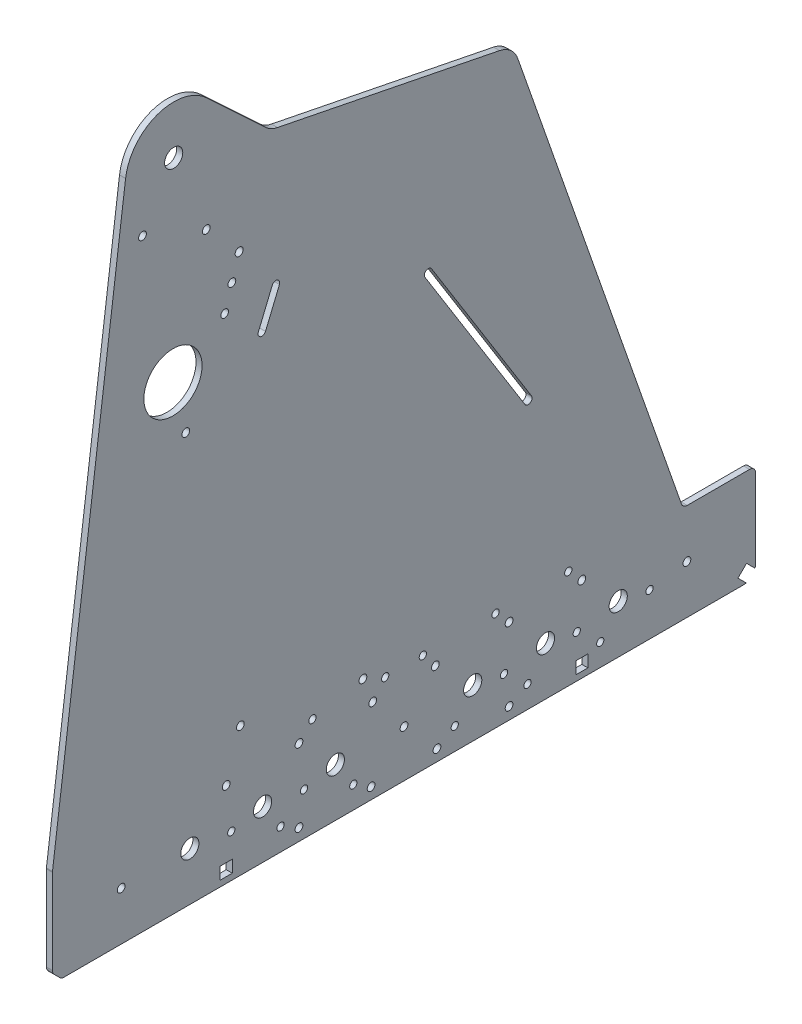
SolidWorks part; units mm, degrees
ref_plane "Front Plane" through (0, 0, 0) normal (0, 0, 1) x (1, 0, 0)
ref_plane "Top Plane" through (0, 0, 0) normal (0, 1, 0) x (1, 0, 0)
ref_plane "Right Plane" through (0, 0, 0) normal (1, 0, 0) x (0, 0, -1)
sketch "Sketch1" plane through (0, 0, 0) normal (1, 0, 0) x (0, 0, -1)
  line L0 (-184.15, -24.6062) -> (184.15, -24.6062)
  line L1 (184.15, -24.6062) -> (184.15, 26.1938)
  line L2 (184.15, 26.1938) -> (146.05, 26.1937)
  line L3 (146.05, 26.1937) -> (57.15, 280.1938)
  line L5 (-145.839, 321.5609) -> (-184.15, 26.1938)
  line L6 (-184.15, 26.1938) -> (-184.15, -24.6062)
  line L7 (-184.15, 350.0437) -> (184.15, 350.0437) construction
  line L8 (57.15, 280.1938) -> (-69.85, 305.5938)
  line L9 (-69.85, 305.5938) -> (-103.3099, 336.854)
  arc A0 (-103.3099, 336.854) -> (-145.839, 321.5609) centre (-120.65, 318.2937) ccw
  point P8 (0, -24.6062)
  dimension "D1" = 368.3
  dimension "D7" = 25.4
  dimension "D2" = 50.8
  dimension "D3" = 38.1
  dimension "D4" = 24.6062
  dimension "D5" = 374.65
  dimension "D6" = 304.8
  dimension "D8" = 342.9
  dimension "D9" = 127
  dimension "D10" = 304.8
  dimension "D11" = 25.4
  dimension "D12" = 127
extrude "Boss-Extrude1" add sketch "Sketch1" along normal blind 3.175
chamfer "Chamfer1" distance 4.7625 angle 45 2 edges at (1.5875, -24.6062, 184.15) (1.5875, -24.6062, -184.15)
fillet "Fillet1" radius 12.7 2 edges at (1.5875, 305.5938, 69.85) (1.5875, 280.1938, -57.15)
fillet "Fillet2" radius 3.175 3 edges at (1.5875, 26.1938, 184.15) (1.5875, 26.1938, -184.15) (1.5875, 26.1937, -146.05)
fillet "Fillet3" radius 3.175 4 edges at (1.5875, -19.8438, -184.15) (1.5875, -24.6062, -179.3875) (1.5875, -19.8437, 184.15) (1.5875, -24.6062, 179.3875)
sketch "Sketch16" plane through (3.175, 0, 0) normal (1, 0, 0) x (0, 0, -1)
  circle A0 centre (112.1746, 0.7937) radius 4.7625
  circle A1 centre (74.0746, 0.7937) radius 4.7625
  circle A2 centre (35.9746, 0.7937) radius 4.7625
  circle A3 centre (-35.9746, 0.7938) radius 4.7625
  circle A4 centre (-74.0746, 0.7938) radius 4.7625
  circle A5 centre (-112.1746, 0.7937) radius 4.7625
  dimension "D1" = 9.525
  dimension "D2" = 9.525
extrude "Cut-Extrude1" cut sketch "Sketch16" against normal up to next
sketch "Sketch25" plane through (3.175, 0, 0) normal (1, 0, 0) x (0, 0, -1)
  circle A0 centre (102.7672, -13.0003) radius 1.905 construction
  circle A1 centre (86.0486, 27.3622) radius 1.905 construction
  circle A2 centre (128.5804, -2.3081) radius 1.905 construction
  circle A3 centre (102.7672, -13.0003) radius 1.905
  circle A4 centre (86.0486, 27.3622) radius 1.905
  circle A5 centre (128.5804, -2.3081) radius 1.905
  circle A6 centre (64.6672, -13.0003) radius 1.905 construction
  circle A8 centre (-9.8486, 27.3622) radius 1.905 construction
  circle A10 centre (-47.9486, 27.3622) radius 1.905 construction
  circle A11 centre (-90.4804, -2.3081) radius 1.905 construction
  circle A12 centre (-64.6672, -13.0003) radius 1.905 construction
  circle A14 centre (-52.3804, -2.3081) radius 1.905 construction
  circle A15 centre (-26.5672, -13.0003) radius 1.905 construction
  circle A16 centre (9.8486, 27.3622) radius 1.905 construction
  circle A17 centre (26.5672, -13.0003) radius 1.905 construction
  circle A18 centre (47.9486, 27.3622) radius 1.905 construction
  circle A19 centre (52.3804, -2.3081) radius 1.905 construction
  circle A20 centre (90.4804, -2.3081) radius 1.905 construction
  circle A21 centre (-9.8486, 27.3622) radius 1.905
  circle A23 centre (-47.9486, 27.3622) radius 1.905
  circle A24 centre (-90.4804, -2.3081) radius 1.905
  circle A25 centre (-64.6672, -13.0003) radius 1.905
  circle A27 centre (-52.3804, -2.3081) radius 1.905
  circle A28 centre (-26.5672, -13.0003) radius 1.905
  circle A29 centre (9.8486, 27.3622) radius 1.905
  circle A30 centre (26.5672, -13.0003) radius 1.905
  circle A31 centre (47.9486, 27.3622) radius 1.905
  circle A32 centre (64.6672, -13.0003) radius 1.905
  circle A33 centre (52.3804, -2.3081) radius 1.905
  circle A34 centre (90.4804, -2.3081) radius 1.905
extrude "Cut-Extrude4" cut sketch "Sketch25" against normal up to next
sketch "Sketch23" plane through (3.175, 0, 0) normal (1, 0, 0) x (0, 0, -1)
  point P0 (-55.0246, -18.3223)
  point P3 (-55.0246, 19.9098)
  point P6 (-93.1246, 19.9098)
  point P9 (-17.2515, -18.6426)
  point P12 (-16.4124, 19.3854)
  point P15 (16.4124, 19.3854)
  point P18 (17.2515, -18.6426)
  point P21 (55.0246, -18.3223)
  point P27 (93.1246, 19.9098)
  point P30 (55.0246, 19.9098)
hole_wizard "#8 (0.16) Diameter Hole1" positions "Sketch23" profile "Sketch24" hole size "#8" standard "ANSI Inch" end condition up to next
sketch "Sketch24" plane through (3.175, -18.3223, 55.0246) normal (0, 1, 0) x (0, 0, -1)
  line L0 (0, 0) -> (0, 3.175)
  line L1 (0, 3.175) -> (2.032, 3.175)
  line L2 (2.032, 3.175) -> (2.032, 0)
  line L5 (2.032, 0) -> (0, 0)
  line L11 (0, -6.35) -> (0, 107.95) construction
  dimension "Thru Hole Dia." = 4.064
  dimension "Thru Hole Depth" = 3.175
sketch "Sketch22" plane through (3.175, 0, 0) normal (1, 0, 0) x (0, 0, -1)
  line L0 (-96.2996, -15.1473) -> (-89.9496, -15.1473) construction
  line L1 (-96.2996, -15.1473) -> (-89.9496, -15.1473)
  line L2 (-96.2996, -15.1473) -> (-96.2996, -21.4973)
  line L3 (-96.2996, -21.4973) -> (-89.9496, -21.4973)
  line L4 (-89.9496, -15.1473) -> (-89.9496, -21.4973)
  line L5 (-96.2996, -15.1473) -> (-89.9496, -21.4973) construction
  line L6 (-96.2996, -21.4973) -> (-89.9496, -15.1473) construction
  line L7 (-89.9496, -15.1473) -> (-89.9496, -19.8734) construction
  line L77 (179.3875, -24.6062) -> (183.8776, -20.1161)
  line L78 (179.3875, -24.6062) -> (174.8974, -20.1161)
  line L79 (183.8776, -20.1161) -> (179.3875, -15.626)
  line L80 (174.8974, -20.1161) -> (179.3875, -15.626)
  line L81 (180.3174, -23.6763) -> (183.2201, -20.7737) construction
  line L82 (-178.0724, -24.6062) -> (178.0724, -24.6062) construction
  line L84 (89.9496, -21.4973) -> (96.2996, -21.4973)
  line L85 (89.9496, -21.4973) -> (89.9496, -15.1473)
  line L86 (89.9496, -15.1473) -> (96.2996, -15.1473)
  line L87 (96.2996, -21.4973) -> (96.2996, -15.1473)
  line L88 (89.9496, -21.4973) -> (96.2996, -15.1473) construction
  line L89 (89.9496, -15.1473) -> (96.2996, -21.4973) construction
  point P0 (-93.1246, -18.3223)
  point P19 (93.1246, -18.3223)
  dimension "D1" = 6.35
  dimension "D2" = 6.35
extrude "Cut-Extrude3" cut sketch "Sketch22" against normal up to next
sketch "Sketch21" plane through (3.175, 0, 0) normal (1, 0, 0) x (0, 0, -1)
  circle A0 centre (-148.1579, 0.7937) radius 2.032
  circle A2 centre (0, 0) radius 2.032
  circle A3 centre (148.1579, 0.7938) radius 2.032
  dimension "D1" = 4.064
extrude "Cut-Extrude2" cut sketch "Sketch21" against normal up to next
sketch "Sketch26" plane through (3.175, 0, 0) normal (1, 0, 0) x (0, 0, -1)
  line L0 (-145.839, 321.5609) -> (-184.1236, 26.3971) construction
  line L1 (-178.0724, -24.6062) -> (178.0724, -24.6062) construction
  circle A0 centre (-121.0218, 216.6937) radius 15.24
  dimension "D1" = 30.48
  dimension "D2" = 38.1
  dimension "D3" = 241.3
extrude "Cut-Extrude5" cut sketch "Sketch26" against normal through all
sketch "Sketch27" plane through (3.175, 0, 0) normal (1, 0, 0) x (0, 0, -1)
  circle A0 centre (-120.65, 318.2937) radius 4.7625
  dimension "D1" = 9.525
extrude "Cut-Extrude6" cut sketch "Sketch27" against normal through all
sketch "Sketch28" plane through (3.175, 0, 0) normal (1, 0, 0) x (0, 0, -1)
  line L0 (-120.65, 318.2937) -> (-103.5612, 277.2599) construction
  line L1 (-103.5612, 277.2599) -> (-86.3654, 258.566) construction
  line L2 (-86.3654, 258.566) -> (-90.1612, 246.4465) construction
  line L3 (-90.1612, 246.4465) -> (-93.9569, 234.327) construction
  line L4 (-145.839, 321.5609) -> (-184.1236, 26.3971) construction
  circle A0 centre (-93.9569, 234.327) radius 2.032
  circle A1 centre (-90.1612, 246.4465) radius 2.032
  circle A2 centre (-86.3654, 258.566) radius 2.0955
  circle A3 centre (-103.5612, 277.2599) radius 2.032
  dimension "D4" = 4.064
  dimension "D5" = 4.191
  dimension "D6" = 4.064
  dimension "D1" = 25.4
  dimension "D2" = 44.45
  dimension "D3" = 12.7
  dimension "D7" = 30
  dimension "D8" = 120
  dimension "D9" = 160
extrude "Cut-Extrude7" cut sketch "Sketch28" against normal through all
sketch "Sketch29" plane through (3.175, 0, 0) normal (1, 0, 0) x (0, 0, -1)
  line L0 (-145.839, 321.5609) -> (-184.1236, 26.3971) construction
  line L1 (-67.1375, 233.9197) -> (-74.4276, 216.3198) construction
  line L2 (-65.2602, 233.1421) -> (-72.5503, 215.5422)
  line L3 (-69.0148, 234.6973) -> (-76.305, 217.0974)
  line L4 (-67.1375, 233.9197) -> (-67.1375, 253.7354) construction
  circle A0 centre (-136.9875, 291.0697) radius 2.032
  circle A2 centre (-120.65, 318.2937) radius 4.7625 construction
  arc A4 (-65.2602, 233.1421) -> (-69.0148, 234.6973) centre (-67.1375, 233.9197) ccw
  arc A5 (-76.305, 217.0974) -> (-72.5503, 215.5422) centre (-74.4276, 216.3198) ccw
  point P8 (-70.7826, 225.1198)
  dimension "D1" = 31.75
  dimension "D2" = 4.064
  dimension "D3" = 69.85
  dimension "D4" = 12.7
  dimension "D5" = 57.15
  dimension "D6" = 19.05
  dimension "D7" = 22.5
extrude "Cut-Extrude8" cut sketch "Sketch29" against normal through all
sketch "Sketch30" plane through (3.175, 0, 0) normal (1, 0, 0) x (0, 0, -1)
  line L0 (-85.7125, 43.2475) -> (-21.5354, 32.3996) construction
  circle A1 centre (-21.5354, 32.3996) radius 7.9375 construction
  circle A2 centre (-85.7125, 43.2475) radius 2.032
  circle A3 centre (-35.9746, 0.7938) radius 4.7625 construction
  circle A4 centre (-48.1454, 36.8975) radius 19.05 construction
  circle A5 centre (-85.7125, 43.2475) radius 19.05 construction
  circle A6 centre (-21.5354, 32.3996) radius 2.032
  circle A7 centre (-74.0746, 0.7938) radius 4.7625 construction
  point P4 (-48.1454, 36.8975)
  dimension "D2" = 38.1
  dimension "D4" = 15.875
  dimension "D5" = 4.064
  dimension "D6" = 44.45
  dimension "D1" = 38.1
  dimension "D3" = 6.35
extrude "Cut-Extrude9" cut sketch "Sketch30" against normal through all
sketch "Sketch31" plane through (0, 0, 0) normal (-1, 0, 0) x (0, 0, 1)
  circle A1 centre (114.3, 190.5) radius 2.032
  dimension "D1" = 114.3
  dimension "D6" = 4.064
  dimension "D2" = 190.5
extrude "Cut-Extrude10" cut sketch "Sketch31" against normal through all
sketch "Sketch34" plane through (0, 0, 0) normal (-1, 0, 0) x (0, 0, 1)
  line L0 (-65.024, 115.57) -> (-12.7, 199.39) construction
  line L1 (-66.7477, 116.646) -> (-14.4237, 200.466)
  line L2 (-63.3003, 114.494) -> (-10.9763, 198.314)
  arc A0 (-66.7477, 116.646) -> (-63.3003, 114.494) centre (-65.024, 115.57) ccw
  arc A1 (-10.9763, 198.314) -> (-14.4237, 200.466) centre (-12.7, 199.39) ccw
  point P3 (-38.862, 157.48)
  dimension "D5" = 2.032
  dimension "D1" = 115.57
  dimension "D2" = 65.024
  dimension "D3" = 199.39
  dimension "D4" = 12.7
extrude "Cut-Extrude12" cut sketch "Sketch34" against normal through all
